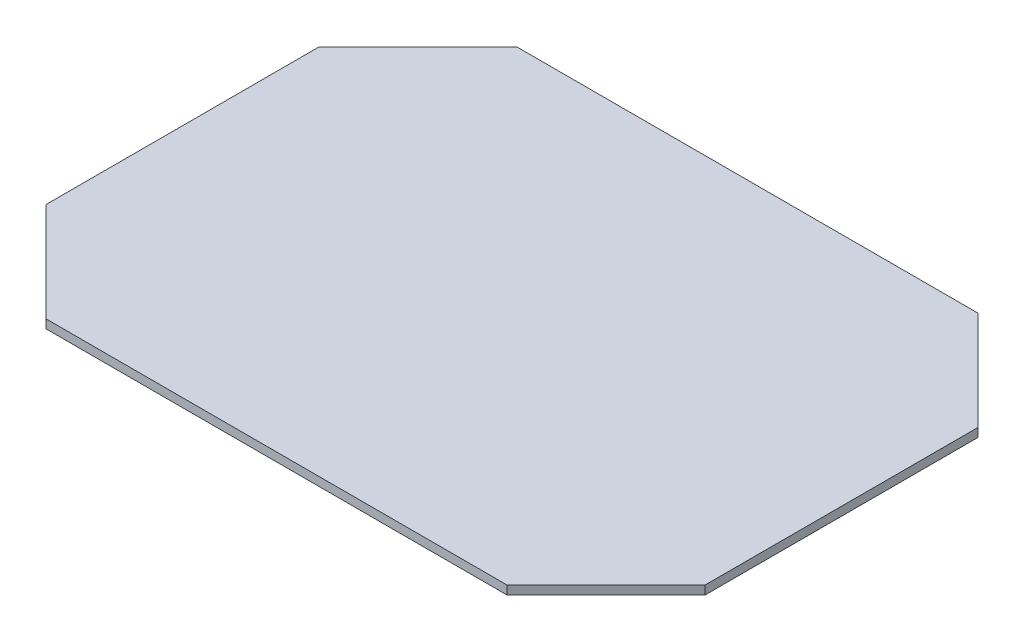
SolidWorks part; units mm, degrees
ref_plane "Front Plane" through (0, 0, 0) normal (0, 0, 1) x (1, 0, 0)
ref_plane "Top Plane" through (0, 0, 0) normal (0, 1, 0) x (1, 0, 0)
ref_plane "Right Plane" through (0, 0, 0) normal (1, 0, 0) x (0, 0, -1)
sketch "Sketch1" plane through (0, 0, 0) normal (0, 1, 0) x (1, 0, 0)
  line L0 (0, 0) -> (163.05, 0) construction
  line L1 (163.05, 0) -> (199.8832, 36.8332) construction
  line L2 (0, 0) -> (-36.8332, 36.8332) construction
  line L3 (-36.8332, 36.8332) -> (-36.8332, 134.8832) construction
  line L4 (199.8832, 36.8332) -> (199.8832, 134.8832) construction
  line L5 (199.8832, 134.8832) -> (163.05, 171.7164) construction
  line L6 (-36.8332, 134.8832) -> (0, 171.7164) construction
  line L7 (0, 171.7164) -> (163.05, 171.7164) construction
  line L8 (1.864, 167.2164) -> (161.186, 167.2164)
  line L9 (195.3832, 133.0192) -> (161.186, 167.2164)
  line L10 (195.3832, 38.6972) -> (195.3832, 133.0192)
  line L11 (161.186, 4.5) -> (195.3832, 38.6972)
  line L12 (1.864, 4.5) -> (161.186, 4.5)
  line L13 (1.864, 4.5) -> (-32.3332, 38.6972)
  line L14 (-32.3332, 38.6972) -> (-32.3332, 133.0192)
  line L15 (-32.3332, 133.0192) -> (1.864, 167.2164)
  dimension "D1" = 4.5
extrude "Boss-Extrude2" add sketch "Sketch1" along normal blind 3
